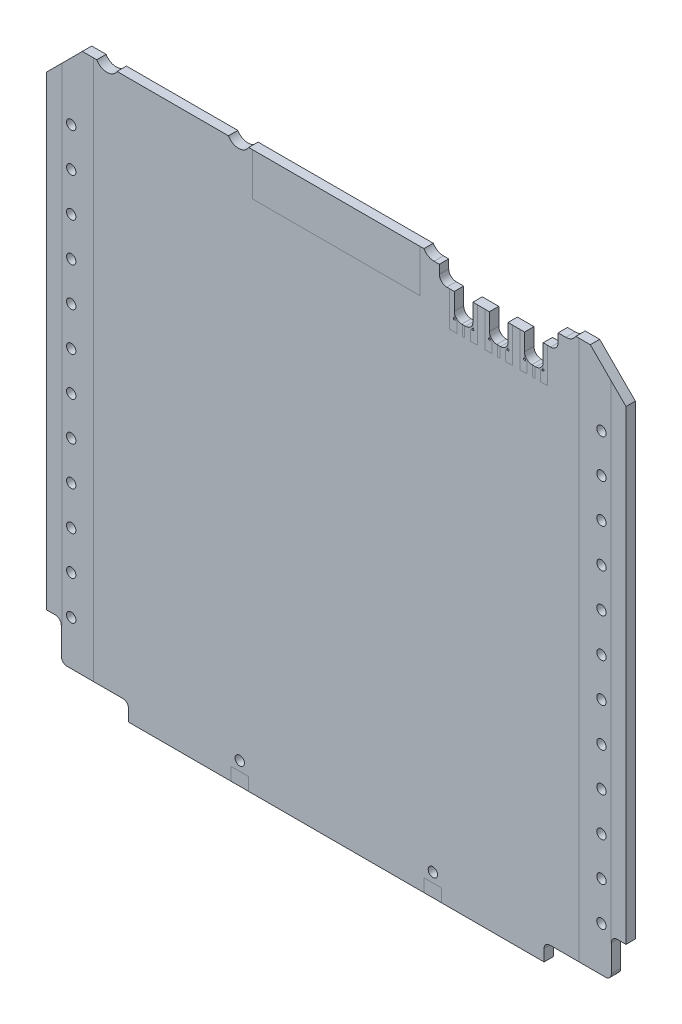
SolidWorks part; units mm, degrees
material "FR4_stuffedProtoboard"
ref_plane "Front Plane" through (0, 0, 0) normal (0, 0, 1) x (1, 0, 0)
ref_plane "Top Plane" through (0, 0, 0) normal (0, 1, 0) x (1, 0, 0)
ref_plane "Right Plane" through (0, 0, 0) normal (1, 0, 0) x (0, 0, -1)
ref_plane "Plane4" through (0, 0, -0.0125) normal (0, 0, -1) x (-1, 0, 0)
sketch "Sketch1" plane through (0, 0, -0.0125) normal (0, 0, -1) x (-1, 0, 0)
  line L4 (49.5, -50) -> (49.5, 45.3)
  line L6 (49.5, 45.3) -> (-49.5, 45.3)
  line L12 (-49.5, 45.3) -> (-49.5, -50)
  line L17 (-49.5, -50) -> (49.5, -50)
  line L18 (0, -50) -> (0, 45.3) construction
  dimension "D7" = 95.3
  dimension "D1" = 99
  dimension "D34" = 50
extrude "basicSize" add sketch "Sketch1" against normal blind 1.6
chamfer "Chamfer1" distance 6.1 angle 45 2 edges at (49.5, 45.3, 0.7875) (-49.5, 45.3, 0.7875)
sketch "Sketch4" plane through (0, 0, 1.5875) normal (0, 0, 1) x (1, 0, 0)
  line L1 (37.4679, 45.3) -> (40.9321, 45.3)
  line L7 (-43.4, 45.3) -> (43.4, 45.3) construction
  line L8 (49.5, 39.2) -> (49.5, -50) construction
  arc A0 (40.9321, 45.3) -> (37.4679, 45.3) centre (39.2, 46.3) cw
  point P5 (39.2, 44.3)
  dimension "D1" = 2
  dimension "D3" = 10.3
  dimension "D2" = 1
extrude "backplaneSideScrewCutout" cut sketch "Sketch4" against normal through all both and the other way through all
pattern_linear "LPattern3" count 2 spacing 22.5 along (-1, 0, 0) of "backplaneSideScrewCutout"
mirror "Mirror3" about plane through (0, 0, 0) normal (1, 0, 0) of "LPattern3"
sketch "Sketch6" plane through (0, 0, 1.5875) normal (0, 0, 1) x (1, 0, 0)
  line L0 (-49.5, -50) -> (-49.5, 39.2) construction
  line L1 (-49.5, -40.4) -> (-47, -40.4)
  line L2 (-49.5, -40.4) -> (-49.5, -50)
  line L4 (-47, -40.4) -> (-47, -47)
  line L5 (49.5, -50) -> (-49.5, -50) construction
  line L6 (-35.5, -50) -> (-49.5, -50)
  line L7 (-35.5, -50) -> (-35.5, -47)
  line L8 (-35.5, -47) -> (-47, -47)
  dimension "D1" = 2.5
  dimension "D2" = 3
  dimension "D3" = 9.6
  dimension "D4" = 14
extrude "Cut-Extrude4" cut sketch "Sketch6" against normal through all
fillet "Fillet1" radius 1 3 edges at (-35.5, -47, 0.7875) (-47, -47, 0.7875) (-47, -40.4, 0.7875)
mirror "Mirror1" about plane through (0, 0, 0) normal (1, 0, 0) of "Cut-Extrude4", "Fillet1"
sketch "Sketch7" plane through (0, 0, 1.5875) normal (0, 0, 1) x (1, 0, 0)
  line L0 (-14.2875, 45.5) -> (-14.2875, 39.912) construction
  line L1 (-14.2875, 45.3) -> (-14.2875, 38.007)
  line L2 (-12.2428, 38.007) -> (-11.8872, 38.007) construction
  line L3 (-14.2875, 38.007) -> (14.2875, 38.007)
  line L4 (14.2875, 45.5) -> (14.2875, 39.912) construction
  line L5 (14.2875, 45.3) -> (14.2875, 38.007)
  line L7 (-14.9679, 45.3) -> (14.9679, 45.3) construction
  line L8 (-14.2875, 45.3) -> (14.2875, 45.3)
extrude "TigerEyeFootprint" cut sketch "Sketch7" against normal blind 0.0001
sketch "thermalContacts_upper" plane through (0, 0, 1.5875) normal (0, 0, 1) x (1, 0, 0)
  line L0 (-49.5, -40.4) -> (-49.5, 39.2) construction
  line L1 (35.5, -50) -> (-35.5, -50) construction
  line L3 (-46.9, 45.3) -> (-46.9, -41.5)
  line L4 (-37.4679, 45.3) -> (-18.4321, 45.3) construction
  line L23 (-46.9, 45.3) -> (-56.3922, 45.3)
  line L24 (-56.3922, 45.3) -> (-56.3922, -41.5)
  line L25 (-56.3922, -41.5) -> (-46.9, -41.5)
  dimension "D1" = 2.6
  dimension "D2" = 8.5
extrude "keepOut_bottom" cut sketch "thermalContacts_upper" against normal blind 0.0001
sketch "Sketch3" plane through (0, 0, 1.5875) normal (0, 0, 1) x (1, 0, 0)
  line L1 (-47, -46) -> (-47, -41.5) construction
  line L2 (-36.5, -47) -> (-46, -47) construction
  line L3 (-14.9679, 45.3) -> (14.9679, 45.3) construction
  line L5 (-49.5, -40.4) -> (-49.5, 39.2) construction
  line L6 (-46.9, -41.5) -> (-46.9, 41.8) construction
  line L7 (-46.9, -41.5) -> (-47, -41.5)
  line L8 (-47, -46) -> (-47, -41.5) construction
  line L9 (-47, -41.5) -> (-46.9, -41.5) construction
  line L10 (0, -50) -> (0, 45.3) construction
  line L11 (35.5, -50) -> (-35.5, -50) construction
  line L12 (-43.4, 45.3) -> (-40.9321, 45.3) construction
  line L13 (-41.5, 45.3) -> (-46.9, 45.3)
  line L14 (-46, -47) -> (-41.5, -47)
  line L15 (-47, -41.5) -> (-47, -46)
  line L16 (-46.9, 45.3) -> (-46.9, -41.5)
  line L17 (-41.5, -47) -> (-41.5, 45.3)
  arc A3 (-47, -46) -> (-46, -47) centre (-46, -46) ccw construction
  arc A4 (-46, -47) -> (-47, -46) centre (-46, -46) cw
  dimension "D1" = 8
extrude "caution_top" cut sketch "Sketch3" against normal blind 0.0001
sketch "hold-downLocations" plane through (0, 0, 1.5875) normal (0, 0, 1) x (1, 0, 0)
  line L1 (-18, -47.8) -> (-15, -47.8) construction
  line L3 (15, -47.8) -> (18, -47.8)
  line L4 (18, -47.8) -> (18, -50)
  line L5 (35.5, -50) -> (-35.5, -50) construction
  line L6 (18, -50) -> (15, -50)
  line L7 (15, -50) -> (15, -47.8)
  line L8 (-15, -47.8) -> (-15, -50) construction
  line L9 (-15, -50) -> (-18, -50) construction
  line L10 (-18, -50) -> (-18, -47.8) construction
  line L11 (0, -50) -> (0, -47.8) construction
  line L12 (-15, -47.8) -> (15, -47.8) construction
  dimension "D1" = 3
  dimension "D2" = 2.2
  dimension "D3" = 3
  dimension "D5" = 30
extrude "hold-downFootprints" cut sketch "hold-downLocations" against normal blind 0.0001
ref_plane "midplane_Z" through (0, 0, 0.7875) normal (0, 0, 1) x (1, 0, 0)
mirror "clearances_top-bottom" about plane through (0, 0, 0.7875) normal (0, 0, 1) of "hold-downFootprints", "caution_top", "keepOut_bottom"
mirror "clearances_side-side" about plane through (0, 0, 0) normal (1, 0, 0) of "clearances_top-bottom"
sketch "Sketch10" plane through (0, 0, -0.0125) normal (0, 0, -1) x (-1, 0, 0)
  line L0 (-15, -47.8) -> (-15, -50) construction
  line L1 (-18, -47.8) -> (-15, -47.8)
  line L2 (-18, -47.8) -> (-18, -44.5)
  line L3 (-18, -44.5) -> (-15, -44.5)
  line L4 (-15, -47.8) -> (-15, -44.5)
  line L5 (-15, -50) -> (15, -50) construction
  line L6 (0, -50) -> (0, -41.5199) construction
  line L7 (15, -47.8) -> (15, -44.5)
  line L8 (18, -44.5) -> (15, -44.5)
  line L9 (18, -47.8) -> (18, -44.5)
  line L10 (18, -47.8) -> (15, -47.8)
  dimension "D1" = 5.5
extrude "bottomsideShelfKeepouts" cut sketch "Sketch10" against normal up to surface (0.0001 mm away) up to face at (16.5, -48.9, -0.0124)
sketch "recommendedBuildArea" [suppressed] plane through (0, 0, 1.5875) normal (0, 0, 1) x (1, 0, 0)
  line L0 (51.1146, 38.007) -> (51.1146, 56.8216) construction
  line L1 (-35.5, -45.5) -> (-46.8, -45.5) construction
  line L2 (-35.5, -47) -> (-35.5, -45.5) construction
  line L3 (35.5, -47) -> (35.5, -45.5) construction
  line L4 (14.2875, 45.3) -> (-14.2875, 45.3)
  line L5 (-14.2875, 45.3) -> (-14.2875, 38.007)
  line L6 (-14.2875, 38.007) -> (14.2875, 38.007)
  line L7 (-46.8, 41.9) -> (-49.5, 39.2)
  line L8 (-49.5, 39.2) -> (-49.5, -40.4)
  line L9 (-49.5, -40.4) -> (-48, -40.4)
  line L10 (-46.8, -41.5) -> (-46.8, 41.9)
  line L11 (-47, -41.4) -> (-47, -41.5)
  line L12 (-47, -41.4) -> (-47, -41.5)
  line L13 (-47, -41.5) -> (-46.8, -41.5)
  line L14 (35.5, -45.5) -> (46.8, -45.5) construction
  line L15 (54.1146, 35.007) -> (54.1146, 77.997)
  line L16 (54.1146, 77.997) -> (43.8, 42.325)
  line L17 (-46.8, -45.5) -> (-46.8, 41.9) construction
  line L20 (43.8, 42.325) -> (43.8, -42.5)
  line L21 (14.2875, 38.007) -> (14.2875, 45.3)
  line L22 (32.5, -42.5) -> (43.8, -42.5)
  line L23 (-14.2875, 45.3) -> (-14.2875, 38.007)
  line L24 (-14.2875, 38.007) -> (51.1146, 38.007)
  line L25 (32.5, -47) -> (32.5, -42.5)
  line L26 (32.5, -47) -> (32.5, -47)
  line L27 (21, -47) -> (32.5, -47)
  line L28 (21, -45) -> (21, -47)
  line L29 (46.8, -41.5) -> (47, -41.5)
  line L30 (46.8, -41.5) -> (47, -41.5)
  line L31 (46.8, 41.9) -> (46.8, -41.5)
  line L32 (48, -40.4) -> (49.5, -40.4)
  line L33 (49.5, -40.4) -> (49.5, 39.2)
  line L34 (49.5, 39.2) -> (46.8, 41.9)
  line L35 (47, -41.5) -> (47, -41.4)
  line L36 (12, -45) -> (21, -45)
  line L37 (47, -41.5) -> (47, -41.4)
  line L38 (46.8, 41.9) -> (46.8, -45.5) construction
  line L39 (12, -47) -> (12, -45)
  line L40 (-12, -47) -> (12, -47)
  line L41 (-12, -45) -> (-12, -47)
  line L42 (-21, -45) -> (-12, -45)
  line L43 (-21, -47) -> (-21, -45)
  line L44 (-32.5, -47) -> (-21, -47)
  line L45 (-32.5, -47) -> (-32.5, -47)
  line L46 (-32.5, -47) -> (-32.5, -42.5)
  line L47 (-32.5, -42.5) -> (-43.8, -42.5)
  line L48 (-43.8, -42.5) -> (-43.8, 34.7661)
  line L49 (-43.8, 34.7661) -> (-43.8, 34.7661)
  line L50 (-43.8, 34.7661) -> (-39.8793, 42.3)
  line L51 (-17.2875, 42.3) -> (-39.8793, 42.3)
  line L52 (-17.2875, 42.3) -> (-17.2875, 35.007)
  line L53 (-17.2875, 35.007) -> (54.1146, 35.007)
  line L59 (-47, -41.5) -> (-46.8, -41.5)
  line L72 (-15, -48) -> (-15, -50)
  line L73 (-15, -50) -> (15, -50)
  line L74 (15, -50) -> (15, -48)
  line L75 (15, -48) -> (18, -48)
  line L76 (18, -48) -> (18, -50)
  line L77 (18, -50) -> (35.5, -50)
  line L78 (35.5, -50) -> (35.5, -48)
  line L79 (36.5, -47) -> (41.5, -47)
  line L80 (41.5, -47) -> (41.5, 45.3)
  line L81 (41.5, 45.3) -> (40.9321, 45.3)
  line L82 (37.4679, 45.3) -> (34.25, 45.3)
  line L83 (34.25, 45.3) -> (34.25, 38.35)
  line L84 (34.25, 38.35) -> (30.75, 38.35)
  line L85 (30.75, 38.35) -> (30.75, 45.3)
  line L86 (30.75, 45.3) -> (29.25, 45.3)
  line L87 (29.25, 45.3) -> (29.25, 38.35)
  line L88 (29.25, 38.35) -> (25.75, 38.35)
  line L89 (25.75, 38.35) -> (25.75, 45.3)
  line L90 (25.75, 45.3) -> (24.25, 45.3)
  line L91 (24.25, 45.3) -> (24.25, 38.35)
  line L92 (24.25, 38.35) -> (20.75, 38.35)
  line L93 (20.75, 38.35) -> (20.75, 45.3)
  line L94 (20.75, 45.3) -> (18.4321, 45.3)
  line L95 (14.9679, 45.3) -> (14.2875, 45.3)
  line L96 (14.2875, 45.3) -> (14.2875, 38.007)
  line L97 (14.2875, 38.007) -> (-14.2875, 38.007)
  line L98 (-14.2875, 38.007) -> (-14.2875, 45.3)
  line L99 (-14.2875, 45.3) -> (-14.9679, 45.3)
  line L100 (-18.4321, 45.3) -> (-37.4679, 45.3)
  line L101 (-40.9321, 45.3) -> (-41.5, 45.3)
  line L102 (41.5, -47) -> (41.5, 45.3)
  line L103 (-41.5, -47) -> (-36.5, -47)
  line L104 (-35.5, -48) -> (-35.5, -50)
  line L105 (-35.5, -50) -> (-18, -50)
  line L106 (-18, -50) -> (-18, -48)
  line L107 (-18, -48) -> (-15, -48)
  line L108 (-15, -48) -> (-15, -50) construction
  line L109 (-15, -50) -> (15, -50) construction
  line L110 (15, -50) -> (15, -48) construction
  line L111 (15, -48) -> (18, -48) construction
  line L112 (18, -48) -> (18, -50) construction
  line L113 (18, -50) -> (35.5, -50) construction
  line L114 (35.5, -50) -> (35.5, -47) construction
  line L115 (35.5, -47) -> (41.5, -47) construction
  line L133 (51.1146, 38.007) -> (-14.2875, 38.007)
  line L134 (-14.2875, 38.007) -> (-14.2875, 45.3)
  line L136 (-14.2875, 45.3) -> (-41.7, 45.3) construction
  line L139 (-41.5, -47) -> (-35.5, -47) construction
  line L140 (-35.5, -47) -> (-35.5, -50) construction
  line L141 (-35.5, -50) -> (-18, -50) construction
  line L142 (-18, -50) -> (-18, -48) construction
  line L143 (-18, -48) -> (-15, -48) construction
  line L144 (-46.8, 35.5) -> (-41.7, 45.3) construction
  line L160 (-41.5, 45.3) -> (-41.5, -47)
  line L161 (-41.5, 45.3) -> (-41.5, -47)
  line L162 (-46.8, 41.9) -> (-46.8, 35.5) construction
  line L163 (51.1146, 56.8216) -> (46.8, 41.9) construction
  arc A1 (-47, -41.4) -> (-48, -40.4) centre (-48, -41.4) ccw
  arc A3 (48, -40.4) -> (47, -41.4) centre (48, -41.4) ccw
  arc A10 (36.5, -47) -> (35.5, -48) centre (36.5, -48) ccw
  arc A11 (37.4679, 45.3) -> (40.9321, 45.3) centre (39.2, 46.3) ccw
  arc A12 (14.9679, 45.3) -> (18.4321, 45.3) centre (16.7, 46.3) ccw
  arc A13 (-18.4321, 45.3) -> (-14.9679, 45.3) centre (-16.7, 46.3) ccw
  arc A14 (-40.9321, 45.3) -> (-37.4679, 45.3) centre (-39.2, 46.3) ccw
  arc A15 (-35.5, -48) -> (-36.5, -47) centre (-36.5, -48) ccw
  dimension "D5" = 1.5
  dimension "D1" = 0
  dimension "D2" = 0
  dimension "D3" = 0
  dimension "D4" = 0
  dimension "D6" = 3
ref_point "rail midpoint"
sketch "locatorSketch" plane through (0, 0, 1.5875) normal (0, 0, 1) x (1, 0, 0)
  line L0 (-12.2428, 39.531) -> (12.2428, 38.007) construction
  line L1 (12.2428, 39.531) -> (-12.2428, 38.007) construction
  line L2 (-21.9628, 39.277) -> (-33.0372, 38.261) construction
  line L3 (-33.0372, 39.277) -> (-21.9628, 38.261) construction
  line L4 (-12.2428, 38.261) -> (-12.2428, 38.007)
  line L5 (-11.8872, 38.261) -> (-12.2428, 38.261)
  line L6 (-11.8872, 38.007) -> (-11.8872, 38.261)
  line L7 (-12.2428, 38.007) -> (-11.8872, 38.007)
  line L8 (-12.2428, 38.261) -> (-12.2428, 38.007)
  line L9 (-11.8872, 38.261) -> (-12.2428, 38.261)
  line L10 (-11.8872, 38.007) -> (-11.8872, 38.261)
  line L11 (-12.2428, 38.007) -> (-11.8872, 38.007)
  line L12 (-12.2428, 39.531) -> (-12.2428, 39.277)
  line L13 (-11.8872, 39.531) -> (-12.2428, 39.531)
  line L14 (-11.8872, 39.277) -> (-11.8872, 39.531)
  line L15 (-12.2428, 39.277) -> (-11.8872, 39.277)
  line L16 (-12.2428, 39.531) -> (-12.2428, 39.277)
  line L17 (-11.8872, 39.531) -> (-12.2428, 39.531)
  line L18 (-11.8872, 39.277) -> (-11.8872, 39.531)
  line L19 (-12.2428, 39.277) -> (-11.8872, 39.277)
  line L20 (11.8872, 39.531) -> (11.8872, 39.277)
  line L21 (12.2428, 39.531) -> (11.8872, 39.531)
  line L22 (12.2428, 39.277) -> (12.2428, 39.531)
  line L23 (11.8872, 39.277) -> (12.2428, 39.277)
  line L24 (11.8872, 39.531) -> (11.8872, 39.277)
  line L25 (12.2428, 39.531) -> (11.8872, 39.531)
  line L26 (12.2428, 39.277) -> (12.2428, 39.531)
  line L27 (11.8872, 39.277) -> (12.2428, 39.277)
  line L28 (11.8872, 38.261) -> (11.8872, 38.007)
  line L29 (12.2428, 38.261) -> (11.8872, 38.261)
  line L30 (12.2428, 38.007) -> (12.2428, 38.261)
  line L31 (11.8872, 38.007) -> (12.2428, 38.007)
  line L32 (11.8872, 38.261) -> (11.8872, 38.007)
  line L33 (12.2428, 38.261) -> (11.8872, 38.261)
  line L34 (12.2428, 38.007) -> (12.2428, 38.261)
  line L35 (11.8872, 38.007) -> (12.2428, 38.007)
  line L38 (-21.9628, 39.531) -> (-21.9628, 39.277)
  line L39 (-21.6072, 39.531) -> (-21.9628, 39.531)
  line L40 (-21.6072, 39.277) -> (-21.6072, 39.531)
  line L41 (-21.9628, 39.277) -> (-21.6072, 39.277)
  line L42 (-21.9628, 39.531) -> (-21.9628, 39.277)
  line L43 (-21.6072, 39.531) -> (-21.9628, 39.531)
  line L44 (-21.6072, 39.277) -> (-21.6072, 39.531)
  line L45 (-21.9628, 39.277) -> (-21.6072, 39.277)
  line L46 (-33.3928, 38.261) -> (-33.3928, 38.007)
  line L47 (-33.0372, 38.261) -> (-33.3928, 38.261)
  line L48 (-33.0372, 38.007) -> (-33.0372, 38.261)
  line L49 (-33.3928, 38.007) -> (-33.0372, 38.007)
  line L50 (-33.3928, 38.261) -> (-33.3928, 38.007)
  line L51 (-33.0372, 38.261) -> (-33.3928, 38.261)
  line L52 (-33.0372, 38.007) -> (-33.0372, 38.261)
  line L53 (-33.3928, 38.007) -> (-33.0372, 38.007)
  line L55 (-21.9628, 38.261) -> (-21.9628, 38.007)
  line L56 (-21.6072, 38.261) -> (-21.9628, 38.261)
  line L57 (-21.6072, 38.007) -> (-21.6072, 38.261)
  line L58 (-21.9628, 38.007) -> (-21.6072, 38.007)
  line L59 (-21.9628, 38.261) -> (-21.9628, 38.007)
  line L60 (-21.6072, 38.261) -> (-21.9628, 38.261)
  line L61 (-21.6072, 38.007) -> (-21.6072, 38.261)
  line L62 (-21.9628, 38.007) -> (-21.6072, 38.007)
  line L63 (-33.3928, 39.531) -> (-33.3928, 39.277)
  line L64 (-33.0372, 39.531) -> (-33.3928, 39.531)
  line L65 (-33.0372, 39.277) -> (-33.0372, 39.531)
  line L66 (-33.3928, 39.277) -> (-33.0372, 39.277)
  line L67 (-33.3928, 39.531) -> (-33.3928, 39.277)
  line L68 (-33.0372, 39.531) -> (-33.3928, 39.531)
  line L69 (-33.0372, 39.277) -> (-33.0372, 39.531)
  line L70 (-33.3928, 39.277) -> (-33.0372, 39.277)
  dimension "D1" = 0
  dimension "D2" = 0
  dimension "D3" = 0
  dimension "D4" = 0
  dimension "D5" = 0
  dimension "D6" = 0
  dimension "D7" = 0
  dimension "D8" = 0
sketch "Sketch8" plane through (0, 0, 1.5875) normal (0, 0, 1) x (1, 0, 0)
  line L0 (-49.5, -40.4) -> (-48, -40.4) construction
  line L2 (-49.5, -40.4) -> (-49.5, 39.2) construction
  line L3 (-41.5, 45.3) -> (-43.4, 45.3) construction
  line L4 (-18, -47.8) -> (-15, -47.8) construction
  line L5 (-45.3, 33.5) -> (-46.9, 33.5) construction
  line L6 (-46.9, 41.8) -> (-46.9, -41.5) construction
  line L7 (-16.5, -46.2) -> (-16.5, -47.8) construction
  line L8 (-18, -47.8) -> (-15, -47.8) construction
  circle A0 centre (-45.3, 33.5) radius 0.8
  circle A1 centre (-45.3, 26.8727) radius 0.8
  circle A2 centre (-45.3, 20.2455) radius 0.8
  circle A3 centre (-45.3, 13.6182) radius 0.8
  circle A4 centre (-45.3, 6.9909) radius 0.8
  circle A5 centre (-45.3, 0.3636) radius 0.8
  circle A6 centre (-45.3, -6.2636) radius 0.8
  circle A7 centre (-45.3, -12.8909) radius 0.8
  circle A8 centre (-45.3, -19.5182) radius 0.8
  circle A9 centre (-45.3, -26.1455) radius 0.8
  circle A10 centre (-45.3, -32.7727) radius 0.8
  circle A11 centre (-45.3, -39.4) radius 0.8
  circle A12 centre (-16.5, -46.2) radius 0.8
  point P35 (-16.5, -47.8)
  dimension "D1" = 1.6
  dimension "D3" = 1
  dimension "D5" = 4.2
  dimension "D6" = 11.8
  dimension "D2" = 12
extrude "springPinHoleSeed" cut sketch "Sketch8" against normal blind 10
mirror "Mirror4" about plane through (0, 0, 0) normal (1, 0, 0) of "springPinHoleSeed"
sketch "Sketch9" plane through (0, 0, 1.5875) normal (0, 0, 1) x (1, 0, 0)
  circle A0 centre (-45.3, 33.5) radius 1.35
  dimension "D1" = 2.7
sketch "bottomsideKeepout_trace" plane through (0, 0, -0.0125) normal (0, 0, -1) x (-1, 0, 0)
  line L0 (18, -50) -> (18, -44.5) construction
  line L1 (18, -44.5) -> (15, -44.5) construction
  line L2 (15, -44.5) -> (15, -50) construction
  line L3 (-15, -44.5) -> (-15, -50) construction
  line L4 (-15, -44.5) -> (-18, -44.5) construction
  line L5 (-18, -50) -> (-18, -44.5) construction
  line L6 (18, -50) -> (18, -44.5)
  line L7 (18, -44.5) -> (15, -44.5)
  line L8 (15, -44.5) -> (15, -50)
  line L9 (-15, -44.5) -> (-15, -50)
  line L10 (-15, -44.5) -> (-18, -44.5)
  line L11 (-18, -50) -> (-18, -44.5)
  line L12 (15, -50) -> (18, -50) construction
  line L13 (-15, -50) -> (-18, -50) construction
  line L14 (15, -50) -> (18, -50)
  line L15 (-15, -50) -> (-18, -50)
sketch "Sketch11" plane through (0, 0, 1.5875) normal (0, 0, 1) x (1, 0, 0)
  line L0 (49.5, 39.2) -> (49.5, -40.4) construction
  line L6 (35.34, 41.56) -> (32.16, 41.56)
  line L8 (35.34, 41.56) -> (35.34, 37.36)
  line L11 (35.34, 37.36) -> (32.16, 37.36)
  line L12 (32.16, 41.56) -> (32.16, 37.36)
  line L13 (35.34, 41.56) -> (32.16, 37.36) construction
  line L14 (35.34, 37.36) -> (32.16, 41.56) construction
  line L18 (29.34, 41.56) -> (26.16, 41.56)
  line L19 (29.34, 41.56) -> (29.34, 37.36)
  line L20 (29.34, 37.36) -> (26.16, 37.36)
  line L21 (26.16, 41.56) -> (26.16, 37.36)
  line L22 (29.34, 41.56) -> (26.16, 37.36) construction
  line L23 (29.34, 37.36) -> (26.16, 41.56) construction
  line L24 (23.34, 41.56) -> (20.16, 41.56)
  line L25 (23.34, 41.56) -> (23.34, 37.36)
  line L26 (23.34, 37.36) -> (20.16, 37.36)
  line L27 (20.16, 41.56) -> (20.16, 37.36)
  line L28 (23.34, 41.56) -> (20.16, 37.36) construction
  line L29 (23.34, 37.36) -> (20.16, 41.56) construction
  line L30 (18.4321, 45.3) -> (37.4679, 45.3) construction
  line L31 (16.7, 46.3) -> (39.2, 46.3) construction
  point P4 (33.75, 39.46)
  point P10 (27.95, 46.3)
  point P15 (27.75, 39.46)
  point P20 (21.75, 39.46)
  dimension "D5" = 6
  dimension "D1" = 3.18
  dimension "D2" = 4.2
  dimension "D3" = 21.75
  dimension "D4" = 3
  dimension "D6" = 3.74
extrude "Cut-Extrude5" cut sketch "Sketch11" against normal blind 10
fillet "Fillet2" radius 1.27 6 edges at (23.34, 37.36, 0.7875) (29.34, 37.36, 0.7875) (35.34, 37.36, 0.7875) (32.16, 37.36, 0.7875) (26.16, 37.36, 0.7875) (20.16, 37.36, 0.7875)
hole_wizard "Ø0.32 (0.32) Diameter Hole1" positions "Sketch12" profile "Sketch13" hole size "Ø0.32" standard "ANSI Metric"
sketch "Sketch12" plane through (0, 0, 1.5875) normal (0, 0, 1) x (1, 0, 0)
  line L1 (35.34, 38.63) -> (35.34, 41.56) construction
  line L2 (32.16, 41.56) -> (32.16, 38.63) construction
  line L3 (33.75, 37.36) -> (34.7997, 37.36) construction
  line L4 (33.43, 37.36) -> (34.07, 37.36) construction
  point P0 (35.34, 37.52)
  point P2 (32.16, 37.52)
  point P16 (29.34, 37.52)
  point P17 (26.16, 37.52)
  point P18 (23.34, 37.52)
  point P19 (20.16, 37.52)
  dimension "D2" = 6
  dimension "D3" = 0.16
  dimension "D1" = 3
sketch "Sketch13" plane through (35.34, 37.52, 1.5875) normal (1, 0, 0) x (0, -1, 0)
  line L0 (0, 0) -> (0, 9.6211)
  line L1 (0, 9.6211) -> (0.16, 9.525)
  line L2 (0.16, 9.525) -> (0.16, 0)
  line L5 (0.16, 0) -> (0, 0)
  line L10 (0, 9.6211) -> (-0.16, 9.525) construction
  line L11 (0, -6.35) -> (0, 107.95) construction
  dimension "Hole Dia." = 0.32
  dimension "Hole Depth" = 9.525
  dimension "Drill Angle" = 118
sketch "Sketch14" plane through (0, 0, 1.5875) normal (0, 0, 1) x (1, 0, 0)
  line L1 (36.125, 41.56) -> (35.34, 41.56)
  line L2 (36.125, 41.56) -> (36.125, 35.57)
  line L3 (36.125, 35.57) -> (34.895, 35.57)
  line L4 (31.375, 41.56) -> (31.375, 35.57)
  line L5 (36.125, 41.56) -> (31.375, 35.57) construction
  line L6 (36.125, 35.57) -> (31.375, 41.56) construction
  line L7 (33.75, 37.36) -> (33.75, 35.57) construction
  line L8 (33.43, 37.36) -> (34.07, 37.36) construction
  line L9 (32.605, 35.57) -> (32.605, 37.36)
  line L10 (33.56, 37.36) -> (33.94, 37.36)
  line L11 (33.56, 37.36) -> (33.56, 35.57)
  line L12 (33.56, 35.57) -> (33.94, 35.57)
  line L13 (33.94, 37.36) -> (33.94, 35.57)
  line L14 (33.56, 37.36) -> (33.94, 35.57) construction
  line L15 (33.56, 35.57) -> (33.94, 37.36) construction
  line L16 (34.895, 35.57) -> (34.895, 37.36)
  line L17 (33.94, 35.57) -> (33.56, 35.57)
  line L18 (32.16, 41.56) -> (32.16, 38.63) construction
  line L19 (35.34, 38.63) -> (35.34, 41.56) construction
  line L20 (32.16, 41.56) -> (32.16, 38.63)
  line L21 (35.34, 38.63) -> (35.34, 41.56)
  line L22 (33.56, 37.36) -> (33.94, 37.36)
  line L23 (32.16, 41.56) -> (31.375, 41.56)
  line L24 (32.605, 37.36) -> (32.16, 37.36)
  line L25 (34.895, 37.36) -> (35.34, 37.36)
  line L26 (32.16, 37.68) -> (32.16, 38.63)
  line L27 (35.34, 37.68) -> (35.34, 38.63)
  line L28 (32.605, 35.57) -> (31.375, 35.57)
  circle A2 centre (32.16, 37.52) radius 0.16 construction
  circle A3 centre (35.34, 37.52) radius 0.16 construction
  arc A6 (32.16, 37.68) -> (32.16, 37.36) centre (32.16, 37.52) ccw
  arc A7 (35.34, 37.36) -> (35.34, 37.68) centre (35.34, 37.52) ccw
  point P4 (33.75, 38.565)
  point P15 (33.75, 36.465)
  dimension "D1" = 5.99
  dimension "D2" = 4.75
  dimension "D3" = 2.29
  dimension "D4" = 0.38
extrude "Boss-Extrude1" add sketch "Sketch14" along normal blind 0.0001 contours A6 L26 L20 L23 L4 L28 L9 L24 | L13 L10 L11 L12 | A7 L25 L16 L3 L2 L1 L21 L27 region at (35.6451, 38.2662, 1.5875) region at (31.8549, 38.2662, 1.5875) region at (33.75, 36.465, 1.5875)
pattern_linear "LPattern4" count 3 spacing 6 along (-1, 0, 0) of "Boss-Extrude1"
sketch "Sketch15" plane through (0, 0, 1.5875) normal (0, 0, 1) x (1, 0, 0)
  line L0 (18.4321, 45.3) -> (37.4679, 45.3) construction
  line L1 (17.605, 45.3) -> (37.895, 45.3)
  line L2 (17.605, 44.3) -> (17.605, 42.83)
  line L3 (18.875, 41.56) -> (36.625, 41.56)
  line L4 (37.895, 44.3) -> (37.895, 42.83)
  line L5 (17.605, 45.3) -> (37.895, 41.56) construction
  line L6 (17.605, 41.56) -> (37.895, 45.3) construction
  line L7 (35.34, 41.56) -> (32.16, 41.56) construction
  line L8 (19.375, 41.56) -> (19.375, 35.57) construction
  line L9 (36.125, 41.56) -> (36.125, 35.57) construction
  line L11 (37.895, 45.3) -> (39.2, 45.3)
  line L13 (37.895, 44.3) -> (39.2, 44.3)
  line L14 (39.2, 45.3) -> (39.2, 44.3)
  line L15 (37.895, 45.3) -> (39.2, 44.3) construction
  line L16 (37.895, 44.3) -> (39.2, 45.3) construction
  line L17 (16.7, 44.3) -> (17.605, 44.3)
  line L18 (16.7, 44.3) -> (16.7, 45.3)
  line L19 (16.7, 45.3) -> (17.605, 45.3)
  line L21 (16.7, 44.3) -> (17.605, 45.3) construction
  line L22 (16.7, 45.3) -> (17.605, 44.3) construction
  arc A0 (36.625, 41.56) -> (37.895, 42.83) centre (36.625, 42.83) ccw
  arc A1 (17.605, 42.83) -> (18.875, 41.56) centre (18.875, 42.83) ccw
  arc A5 (37.4679, 45.3) -> (40.9321, 45.3) centre (39.2, 46.3) ccw construction
  arc A6 (14.9679, 45.3) -> (18.4321, 45.3) centre (16.7, 46.3) ccw construction
  point P4 (27.75, 43.43)
  point P22 (38.5475, 44.8)
  point P28 (17.1525, 44.8)
  dimension "D3" = 1.27
  dimension "D1" = 0.5
  dimension "D2" = 0.5
extrude "Cut-Extrude6" cut sketch "Sketch15" against normal through all and the other way through all
fillet "Fillet3" [suppressed] radius 0.5
